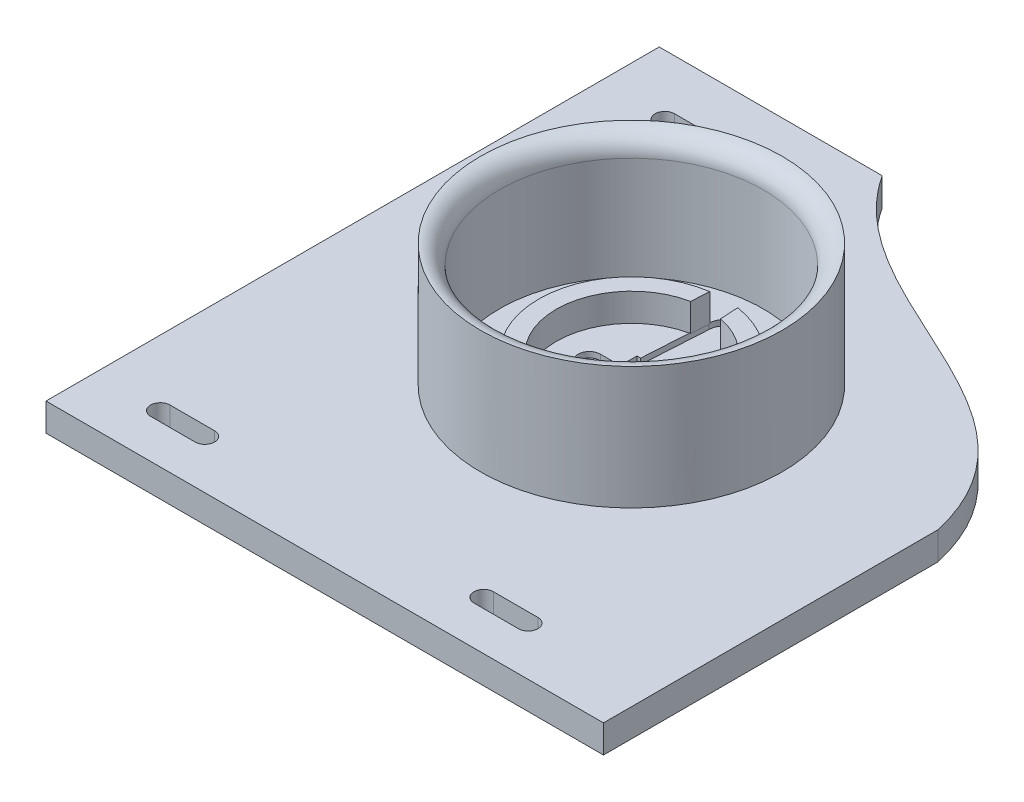
SolidWorks part; units mm, degrees
ref_plane "Plan de face" through (0, 0, 0) normal (0, 0, 1) x (1, 0, 0)
ref_plane "Plan de dessus" through (0, 0, 0) normal (0, 1, 0) x (1, 0, 0)
ref_plane "Plan de droite" through (0, 0, 0) normal (1, 0, 0) x (0, 0, -1)
sketch "Esquisse1" plane through (0, 0, 0) normal (0, 1, 0) x (1, 0, 0)
  line L0 (-50, 55) -> (-10, 55)
  line L1 (-50, -55) -> (50, -55)
  line L2 (-50, -55) -> (-50, 55)
  line L5 (50, -55) -> (50, 5)
  spline S0 degree 3 poles (-10, 55) (5.1488, 31.794) (43.1632, 35.1282) (50, 5) knots 0 0 0 0 1 1 1 1
  point P0 (0, 0)
  dimension "D1" = 110
  dimension "D2" = 100
  dimension "D3" = 40
  dimension "D4" = 60
extrude "Boss.-Extru.1" add sketch "Esquisse1" along normal blind 5
sketch "Esquisse3" plane through (0, 5, 0) normal (0, 1, 0) x (1, 0, 0)
  line L0 (-38.25, 44.25) -> (-30.25, 44.25) construction
  line L1 (-38.25, 46) -> (-30.25, 46)
  line L2 (-38.25, 42.5) -> (-30.25, 42.5)
  line L3 (-50, 55) -> (-50, -55) construction
  line L4 (-10, 55) -> (-50, 55) construction
  line L5 (-38.25, -46.25) -> (-30.25, -46.25) construction
  line L6 (-38.25, -44.5) -> (-30.25, -44.5)
  line L7 (-38.25, -48) -> (-30.25, -48)
  line L8 (19.75, -46.25) -> (27.75, -46.25) construction
  line L9 (19.75, -44.5) -> (27.75, -44.5)
  line L10 (19.75, -48) -> (27.75, -48)
  arc A0 (-38.25, 46) -> (-38.25, 42.5) centre (-38.25, 44.25) ccw
  arc A1 (-30.25, 42.5) -> (-30.25, 46) centre (-30.25, 44.25) ccw
  arc A2 (-38.25, -44.5) -> (-38.25, -48) centre (-38.25, -46.25) ccw
  arc A3 (-30.25, -48) -> (-30.25, -44.5) centre (-30.25, -46.25) ccw
  arc A4 (19.75, -44.5) -> (19.75, -48) centre (19.75, -46.25) ccw
  arc A5 (27.75, -48) -> (27.75, -44.5) centre (27.75, -46.25) ccw
  point P2 (-34.25, 44.25)
  point P7 (-40, 44.25)
  point P10 (-34.25, 46)
  point P17 (-34.25, -46.25)
  point P23 (23.75, -46.25)
  dimension "D1" = 10
  dimension "D5" = 2
  dimension "D2" = 9
  dimension "D4" = 87
  dimension "D3" = 2
extrude "Enlèv. mat.-Extru.1" cut sketch "Esquisse3" against normal blind 15
sketch "Esquisse4" plane through (0, 5, 0) normal (0, 1, 0) x (1, 0, 0)
  line L1 (-4, -5) -> (4, -5)
  line L2 (-4, -5) -> (-4, 5)
  line L3 (-4, 5) -> (4, 5)
  line L4 (4, -5) -> (4, 5)
  line L5 (-4, -5) -> (4, 5) construction
  line L6 (-4, 5) -> (4, -5) construction
  point P0 (0, 0)
  dimension "D1" = 8
  dimension "D2" = 10
extrude "Enlèv. mat.-Extru.2" cut sketch "Esquisse4" against normal blind 2.5
sketch "Esquisse6" plane through (0, 5, 0) normal (0, 1, 0) x (1, 0, 0)
  line L1 (-0.1283, 0.0936) -> (-0.1283, 16.5936) construction
  line L2 (-2.6283, 16.5936) -> (-3.6283, 0.0936)
  line L3 (2.3717, 16.5936) -> (3.3717, 0.0936)
  line L4 (2.3717, -16.4064) -> (3.3717, 0.0936)
  line L5 (-2.6283, -16.4064) -> (-3.6283, 0.0936)
  circle A0 centre (-0.1283, 0.0936) radius 3.5
  arc A1 (-2.6283, 16.5936) -> (2.3717, 16.5936) centre (-0.1283, 16.5936) cw
  arc A2 (-2.6283, -16.4064) -> (2.3717, -16.4064) centre (-0.1283, -16.4064) ccw
extrude "Enlèv. mat.-Extru.3" cut sketch "Esquisse6" against normal blind 1
sketch "Esquisse7" plane through (0, 5, 0) normal (0, 1, 0) x (1, 0, 0)
  line L0 (-7.55, 0) -> (7.55, 0) construction
  line L1 (-7.55, 2) -> (7.55, 2)
  line L2 (-7.55, -2) -> (7.55, -2)
  arc A0 (-7.55, 2) -> (-7.55, -2) centre (-7.55, 0) ccw
  arc A1 (7.55, -2) -> (7.55, 2) centre (7.55, 0) ccw
  point P2 (0, 0)
  dimension "D2" = 0
extrude "Enlèv. mat.-Extru.4" cut sketch "Esquisse7" against normal blind 1
sketch "Esquisse8" plane through (0, 5, 0) normal (0, 1, 0) x (1, 0, 0)
  line L0 (-2.462, 16.5318) -> (-2.6584, 13.2916)
  line L1 (2.538, 16.5318) -> (2.7344, 13.2916)
  line L2 (-2.6584, -13.228) -> (-2.462, -16.4682)
  line L3 (2.7344, -13.228) -> (2.538, -16.4682)
  arc A0 (-2.462, 16.5318) -> (-2.462, -16.4682) centre (0.038, 0.0318) ccw
  arc A1 (2.538, 16.5318) -> (2.538, -16.4682) centre (0.038, 0.0318) cw
  arc A2 (2.7344, 13.2916) -> (2.7344, -13.228) centre (0.038, 0.0318) cw
  arc A3 (-2.6584, 13.2916) -> (-2.6584, -13.228) centre (0.038, 0.0318) ccw
extrude "Boss.-Extru.2" add sketch "Esquisse8" along normal blind 5
sketch "Esquisse9" plane through (0, 5, 0) normal (0, 1, 0) x (1, 0, 0)
  line L0 (-16.6503, 0.0318) -> (-23.6503, 0)
  circle A0 centre (0, 0) radius 23.6503
  arc A1 (-2.462, 16.5318) -> (-2.462, -16.4682) centre (0.038, 0.0318) ccw construction
  circle A3 centre (0, 0) radius 27.0503
  dimension "D1" = 7
  dimension "D2" = 3.4
extrude "Boss.-Extru.3" add sketch "Esquisse9" along normal blind 22 contours A3 A0
sketch "Esquisse10" plane through (0, 2.5, 0) normal (0, 1, 0) x (1, 0, 0)
  circle A0 centre (0, 0) radius 3.4295
extrude "Enlèv. mat.-Extru.5" cut sketch "Esquisse10" against normal blind 22
fillet "Congé1" radius 3.5 1 edges at (0, 27, 23.6503)
